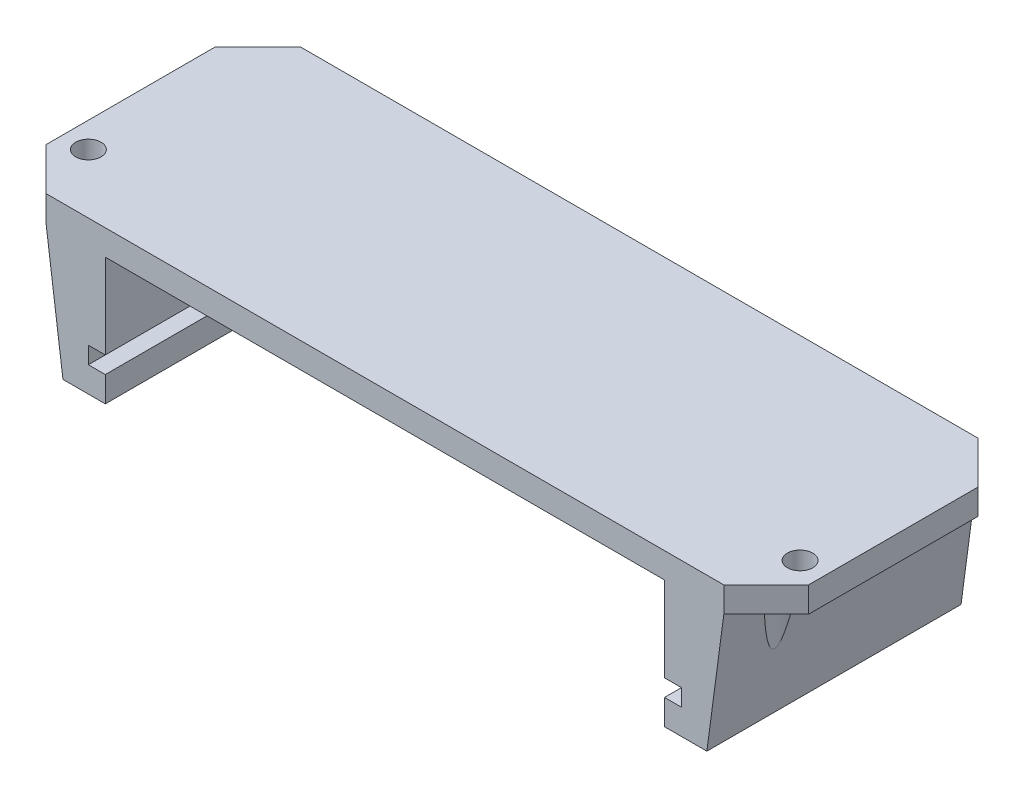
SolidWorks part; units mm, degrees
ref_plane "Front Plane" through (0, 0, 0) normal (0, 0, 1) x (1, 0, 0)
ref_plane "Top Plane" through (0, 0, 0) normal (0, 1, 0) x (1, 0, 0)
ref_plane "Right Plane" through (0, 0, 0) normal (1, 0, 0) x (0, 0, -1)
sketch "Sketch1" plane through (0, 0, 0) normal (0, 0, -1) x (1, 0, 0)
  line L0 (2, -3.1072) -> (2, 6.8928)
  line L1 (-10, -3.1072) -> (80, -3.1072)
  line L2 (-10, -3.1072) -> (-10, -6.1072)
  line L3 (-10, -6.1072) -> (80, -6.1072)
  line L4 (80, -3.1072) -> (80, -6.1072)
  line L5 (2, 6.8928) -> (0, 6.8928)
  line L6 (0, 6.8928) -> (0, 8.8928)
  line L7 (0, 8.8928) -> (2, 8.8928)
  line L8 (2, 8.8928) -> (2, 11.8928)
  line L9 (2, 11.8928) -> (-3, 11.8928)
  line L10 (-3, 11.8928) -> (-5, -3.1072)
  line L11 (68, -3.1072) -> (68, 6.8928)
  line L12 (68, 6.8928) -> (70, 6.8928)
  line L13 (70, 6.8928) -> (70, 8.8928)
  line L14 (70, 8.8928) -> (68, 8.8928)
  line L15 (68, 8.8928) -> (68, 11.8928)
  line L16 (68, 11.8928) -> (73, 11.8928)
  line L17 (73, 11.8928) -> (75, -3.1072)
  dimension "D1" = 3
  dimension "D2" = 90
  dimension "D3" = 2
  dimension "D4" = 2
  dimension "D5" = 10
  dimension "D6" = 3
  dimension "D7" = 7
  dimension "D8" = 70
  dimension "D9" = 5
  dimension "D10" = 12
extrude "Boss-Extrude1" add sketch "Sketch1" along normal blind 30 contours L4 L1 L2 L3 | L9 L10 L1 L0 L5 L6 L7 L8 | L17 L16 L15 L14 L13 L12 L11 L1 region at (-1.1221, -3.794, 0) region at (35, 4.6072, 0) region at (71.1221, -3.794, 0)
sketch "Sketch2" plane through (0, 3.1072, 0) normal (0, -1, 0) x (-1, 0, 0)
  line L0 (10, 30) -> (10, 0) construction
  line L1 (10, 0) -> (-80, 0) construction
  circle A0 centre (7, 7) radius 1.5
  circle A1 centre (-77, 7) radius 1.5
  circle A2 centre (7, 7) radius 3
  circle A3 centre (-77, 7) radius 3
  dimension "D1" = 84
  dimension "D3" = 3
  dimension "D4" = 6
  dimension "D2" = 3
  dimension "D5" = 7
extrude "Cut-Extrude1" cut sketch "Sketch2" against normal blind 20 contours A0 | A1 region at (-7, 3.1072, -7) region at (77, 3.1072, -7)
extrude "Cut-Extrude2" cut sketch "Sketch2<3>" along normal blind 20
sketch "Sketch2<3>" plane through (0, 3.1072, 0) normal (0, -1, 0) x (-1, 0, 0) same geometry as "Sketch2"
chamfer "Chamfer1" distance 5 angle 45 4 edges at (80, 4.6072, 0) (80, 4.6072, -30) (-10, 4.6072, 0) (-10, 4.6072, -30)
